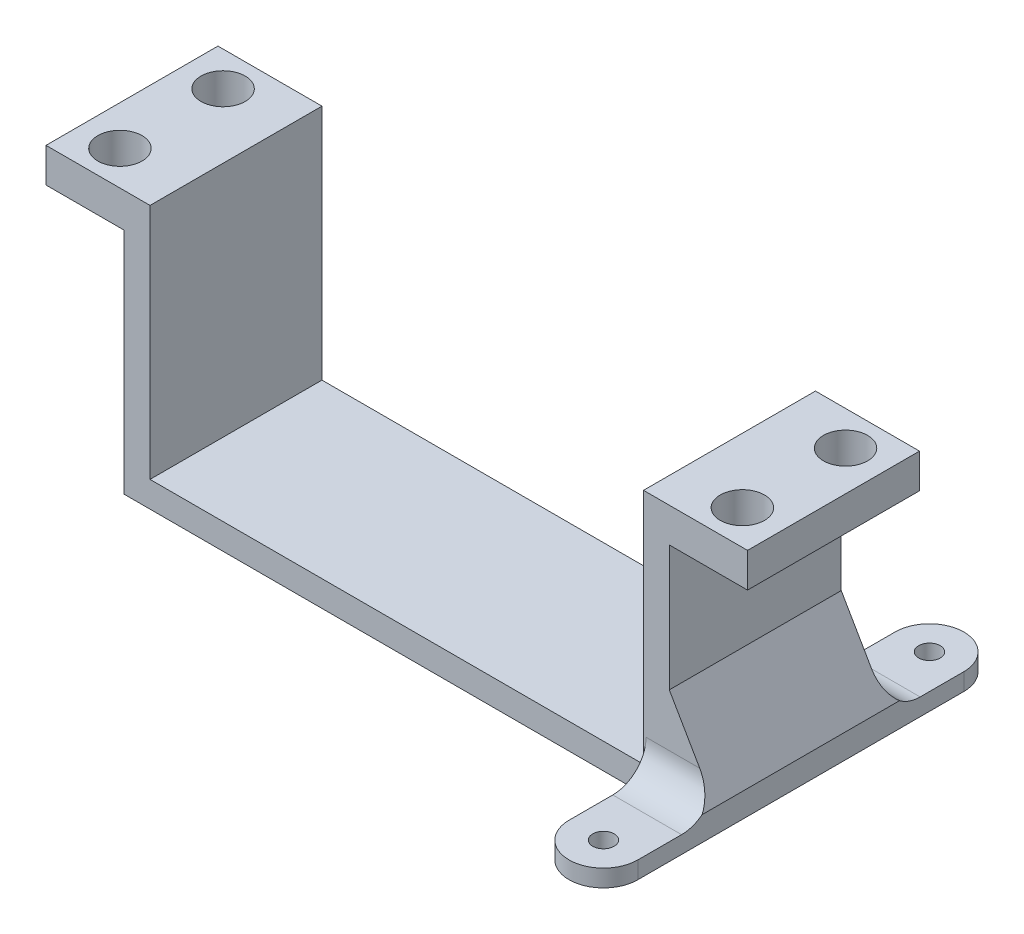
SolidWorks part; units mm, degrees
ref_plane "Front Plane" through (0, 0, 0) normal (0, 0, 1) x (1, 0, 0)
ref_plane "Top Plane" through (0, 0, 0) normal (0, 1, 0) x (1, 0, 0)
ref_plane "Right Plane" through (0, 0, 0) normal (1, 0, 0) x (0, 0, -1)
sketch "Sketch1" plane through (0, 0, 0) normal (0, 0, 1) x (1, 0, 0)
  line L0 (-3.81, 35.052) -> (0, 35.052)
  line L1 (0, 0) -> (72.898, 0)
  line L2 (0, 0) -> (0, 35.052)
  line L4 (72.898, 0) -> (72.898, 35.052)
  line L6 (-3.81, 35.052) -> (-3.81, -3.81)
  line L7 (-3.81, -3.81) -> (76.708, -3.81)
  line L8 (76.708, 35.052) -> (76.708, -3.81)
  line L9 (72.898, 35.052) -> (76.708, 35.052)
  dimension "D1" = 3.81
  dimension "D2" = 3.81
  dimension "D3" = 3.81
  dimension "D4" = 38.862
  dimension "D5" = 72.898
extrude "Boss-Extrude1" add sketch "Sketch1" along normal blind 25.4
sketch "Sketch2" plane through (0, -3.81, 0) normal (0, -1, 0) x (1, 0, 0)
  line L0 (78.359, 36.7792) -> (78.359, -11.3792) construction
  line L1 (76.708, 25.4) -> (76.708, 0) construction
  line L2 (73.279, 36.7792) -> (73.279, -11.3792)
  line L3 (83.439, 36.7792) -> (83.439, -11.3792)
  line L4 (-3.81, 25.4) -> (76.708, 25.4) construction
  circle A0 centre (78.359, 36.7792) radius 1.5875
  circle A1 centre (78.359, -11.3792) radius 1.5875
  arc A2 (83.439, 36.7792) -> (73.279, 36.7792) centre (78.359, 36.7792) ccw
  arc A3 (73.279, -11.3792) -> (83.439, -11.3792) centre (78.359, -11.3792) ccw
  point P4 (78.359, 12.7)
  point P5 (76.708, 12.7)
  point P6 (36.449, 25.4)
  point P9 (78.359, 35.1917)
  point P14 (78.359, -9.7917)
  dimension "D2" = 3.175
  dimension "D3" = 5.08
  dimension "D1" = 44.9834
  dimension "D4" = 41.91
extrude "Boss-Extrude2" add sketch "Sketch2" against normal blind 2.54
sketch "Sketch4" plane through (0, 35.052, 0) normal (0, 1, 0) x (1, 0, 0)
  line L0 (0, -25.4) -> (-3.81, -25.4) construction
  line L1 (0, 0) -> (-15.367, 0)
  line L2 (0, 0) -> (0, -25.4)
  line L3 (0, -25.4) -> (-15.367, -25.4)
  line L4 (-15.367, 0) -> (-15.367, -25.4)
  line L5 (-3.81, -25.4) -> (-3.81, 0) construction
  line L6 (-9.525, -5.08) -> (-9.525, -20.32) construction
  circle A0 centre (-9.525, -5.08) radius 3.2639
  circle A1 centre (-9.525, -20.32) radius 3.2639
  point P13 (-15.367, -12.7)
  point P14 (-9.525, -12.7)
  dimension "D1" = 6.5278
  dimension "D2" = 5.715
  dimension "D3" = 7.62
  dimension "D4" = 5.842
extrude "Boss-Extrude3" add sketch "Sketch4" against normal blind 5.08
ref_plane "Plane1" through (36.449, 0, 0) normal (1, 0, 0) x (0, 0, -1)
mirror "Mirror1" about plane through (36.449, 0, 0) normal (1, 0, 0) of "Boss-Extrude3"
chamfer "Chamfer1" distance 12.7 angle 30 1 edges at (76.708, -1.27, 12.7) first distance on face at (76.708, 14.351, 12.7)
fillet "Fillet1" radius 4.92 2 edges at (78.359, -1.27, 0) (78.359, -1.27, 25.4)
